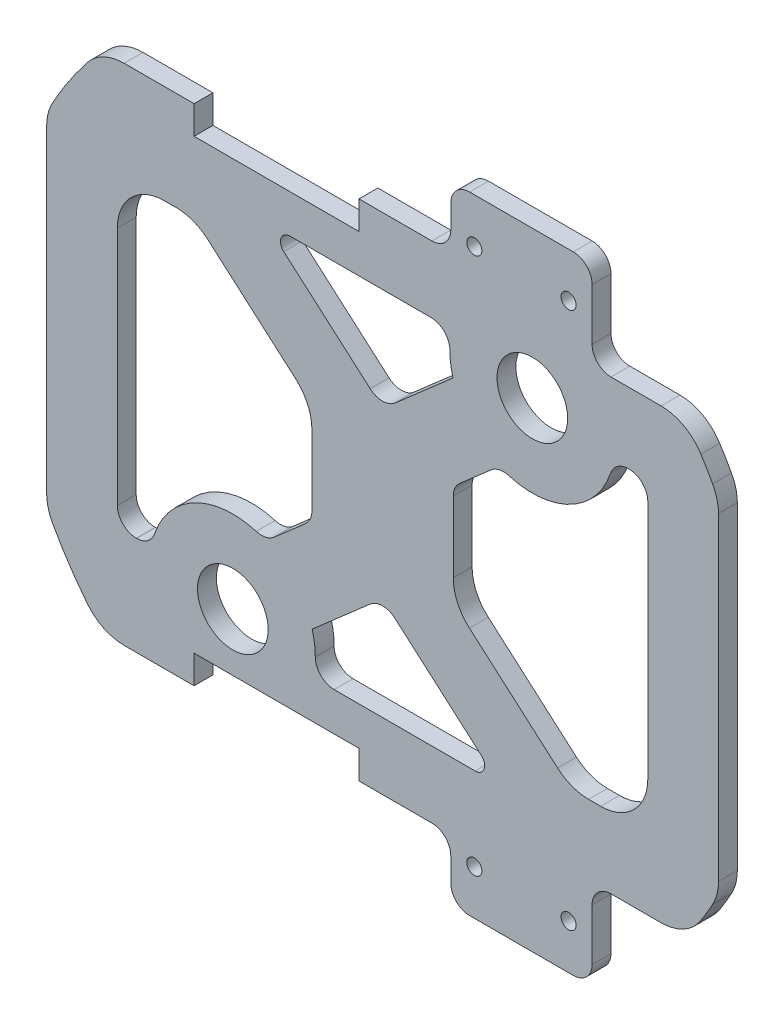
SolidWorks part; units mm, degrees
material "Acrílico (médio-alto impacto)"
ref_plane "Plano frontal" through (0, 0, 0) normal (0, 0, 1) x (1, 0, 0)
ref_plane "Plano superior" through (0, 0, 0) normal (0, 1, 0) x (1, 0, 0)
ref_plane "Plano direito" through (0, 0, 0) normal (1, 0, 0) x (0, 0, -1)
sketch "Esboço1" plane through (0, 0, 0) normal (0, 0, 1) x (1, 0, 0)
  line L0 (80, 0) -> (0, 0) construction
  line L1 (-80, -66.5) -> (80, -66.5)
  line L2 (-80, -66.5) -> (-80, 66.5)
  line L3 (-80, 66.5) -> (80, 66.5)
  line L4 (80, -66.5) -> (80, 66.5)
  line L5 (-80, -66.5) -> (80, 66.5) construction
  line L6 (-80, 66.5) -> (80, -66.5) construction
  line L7 (80, 47.5) -> (-80, 47.5) construction
  line L8 (80, -47.5) -> (-80, -47.5) construction
  line L9 (14.4719, 66.5) -> (14.4719, 53.5)
  line L10 (0, 0) -> (0, 66.5) construction
  line L11 (44.4719, 66.5) -> (44.4719, 47.5)
  line L12 (-5.0035, -47.5) -> (-40.0035, -47.5)
  line L13 (14.4719, -66.5) -> (14.4719, -53.5)
  line L14 (44.4719, 47.5) -> (64.372, 47.5)
  line L15 (28.6277, 47.5) -> (28.6277, 66.5) construction
  line L16 (14.4719, 53.5) -> (-59.479, 53.5)
  line L17 (-40.0035, -53.5) -> (-40.0035, -47.5)
  line L18 (-31.7837, -35.2994) -> (31.7837, 35.2994) construction
  line L24 (-56.2917, 32.5) -> (-39.9802, 32.5)
  line L25 (-39.9802, 32.5) -> (-15, 10.6848)
  line L30 (-15, 10.6848) -> (-15, -10.6848)
  line L31 (-39.9802, -32.5) -> (-15, -10.6848)
  line L36 (-56.2917, -32.5) -> (-39.9802, -32.5)
  line L37 (56.2917, 32.5) -> (39.9802, 32.5)
  line L57 (39.9802, 32.5) -> (15, 10.6848)
  line L58 (15, 10.6848) -> (15, -10.6848)
  line L59 (39.9802, -32.5) -> (15, -10.6848)
  line L60 (56.2917, -32.5) -> (39.9802, -32.5)
  line L61 (-25, -39.3325) -> (0, -17.5)
  line L63 (-25, -39.3325) -> (25, -39.3325)
  line L64 (25, -39.3325) -> (0, -17.5)
  line L65 (-25, 39.3325) -> (0, 17.5)
  line L66 (25, 39.3325) -> (0, 17.5)
  line L67 (-25, 39.3325) -> (25, 39.3325)
  line L69 (-5.0035, -53.5) -> (-40.0035, -53.5)
  line L70 (-5.0035, 53.5) -> (-40.0035, 53.5)
  line L71 (-5.0035, 53.5) -> (-5.0035, 47.5)
  line L72 (-5.0035, 47.5) -> (-40.0035, 47.5)
  line L73 (-40.0035, 53.5) -> (-40.0035, 47.5)
  line L74 (-5.0035, 53.5) -> (-40.0035, 47.5) construction
  line L75 (-5.0035, 47.5) -> (-40.0035, 53.5) construction
  line L76 (-5.0035, -53.5) -> (-5.0035, -47.5)
  line L77 (14.4719, -53.5) -> (-59.479, -53.5)
  line L78 (44.4719, -66.5) -> (44.4719, -47.5)
  line L79 (44.4719, -47.5) -> (64.372, -47.5)
  line L80 (-71.2917, -36.2974) -> (-71.2917, 36.2974)
  line L81 (-56.2917, 32.5) -> (-56.2917, -32.5)
  line L82 (56.2917, 32.5) -> (56.2917, -32.5)
  line L83 (71.2917, -36.2974) -> (71.2917, 36.2974)
  circle A0 centre (0, 0) radius 80
  circle A1 centre (-31.7837, -35.2994) radius 7.5
  circle A2 centre (31.7837, 35.2994) radius 7.5
  circle A3 centre (19.4719, 57) radius 1.6
  circle A8 centre (19.4719, -57) radius 1.6
  arc A9 (-56.2917, -32.5) -> (-56.2917, 32.5) centre (0, 0) cw
  arc A11 (56.2917, -32.5) -> (56.2917, 32.5) centre (0, 0) ccw
  circle A12 centre (-31.7837, -35.2994) radius 17.5
  circle A13 centre (31.7837, 35.2994) radius 17.5
  circle A14 centre (39.4719, 57) radius 1.6
  circle A15 centre (39.4719, -57) radius 1.6
  point P0 (0, 0)
  point P37 (-22.5035, 50.5)
  point P38 (28.6277, 57)
  point P45 (-65, 0)
  point P65 (-22.5035, 53.5)
  dimension "D6" = 15
  dimension "D7" = 3.2
  dimension "D18" = 15
  dimension "D9" = 15
  dimension "D11" = 35
  dimension "D1" = 95
  dimension "D2" = 19
  dimension "D3" = 160
  dimension "D4" = 95
  dimension "D5" = 48
  dimension "D8" = 15
  dimension "D10" = 30
  dimension "D12" = 30
  dimension "D13" = 35
  dimension "D14" = 5
  dimension "D15" = 50
  dimension "D16" = 5
  dimension "D17" = 6
  dimension "D19" = 35
  dimension "D21" = 15
extrude "Ressalto-extrusão1" add sketch "Esboço1" along normal blind 4 contours A0 L13 L1 L12 L17 L3 L9 A13 L37 A11 L60 L59 L58 L57 A12 L36 A9 L24 L25 L30 L31 A3 A14 A8 | L37 A13 L57 A2 | L57 A13 L37 | L67 A13 L66 | L61 A12 L31 A1 L36 L13 L63 | L31 A12 L36 | L63 A12 L61 | A9 L81 | L82 A11 region at (2.3556, -0.5562, 0) region at (-47.0413, -42.87, 0) region at (-38.1575, -24.9182, 0) region at (-17.9859, -36.3042, 0) region at (-59.7958, 0, 0) region at (59.7958, 0, 0) region at (38.1575, 24.9182, 0) region at (44.5193, 32.9814, 0) region at (17.9859, 36.3042, 0)
fillet "Filete2" radius 10 14 edges at (39.9802, -32.5, 2) (15, -10.6848, 2) (-15, 10.6848, 2) (-39.9802, 32.5, 2) (-71.2917, -36.2974, 2) (-71.2917, 36.2974, 2) (-56.2917, 32.5, 2) (56.2917, -32.5, 2) (71.2917, -36.2974, 2) (71.2917, 36.2974, 2) (64.372, 47.5, 2) (64.372, -47.5, 2) (-59.479, 53.5, 2) (-59.479, -53.5, 2)
fillet "Filete3" radius 4 20 edges at (49.0584, 32.5, 2) (24.8078, 19.2499, 2) (15, 10.6848, 2) (-15, -10.6848, 2) (-24.8078, -19.2499, 2) (-49.0584, -32.5, 2) (14.7548, 39.3325, 2) (0, 17.5, 2) (0, -17.5, 2) (-14.7548, -39.3325, 2) (14.4719, 53.5, 2) (14.4719, -53.5, 2) (44.4719, -47.5, 2) (44.4719, 47.5, 2) (14.4719, -66.5, 2) (14.4719, 66.5, 2) (44.4719, 66.5, 2) (44.4719, -66.5, 2) (-56.2917, -32.5, 2) (56.2917, 32.5, 2)
fillet "Filete4" radius 2 2 edges at (25, -39.3325, 2) (-25, 39.3325, 2)
